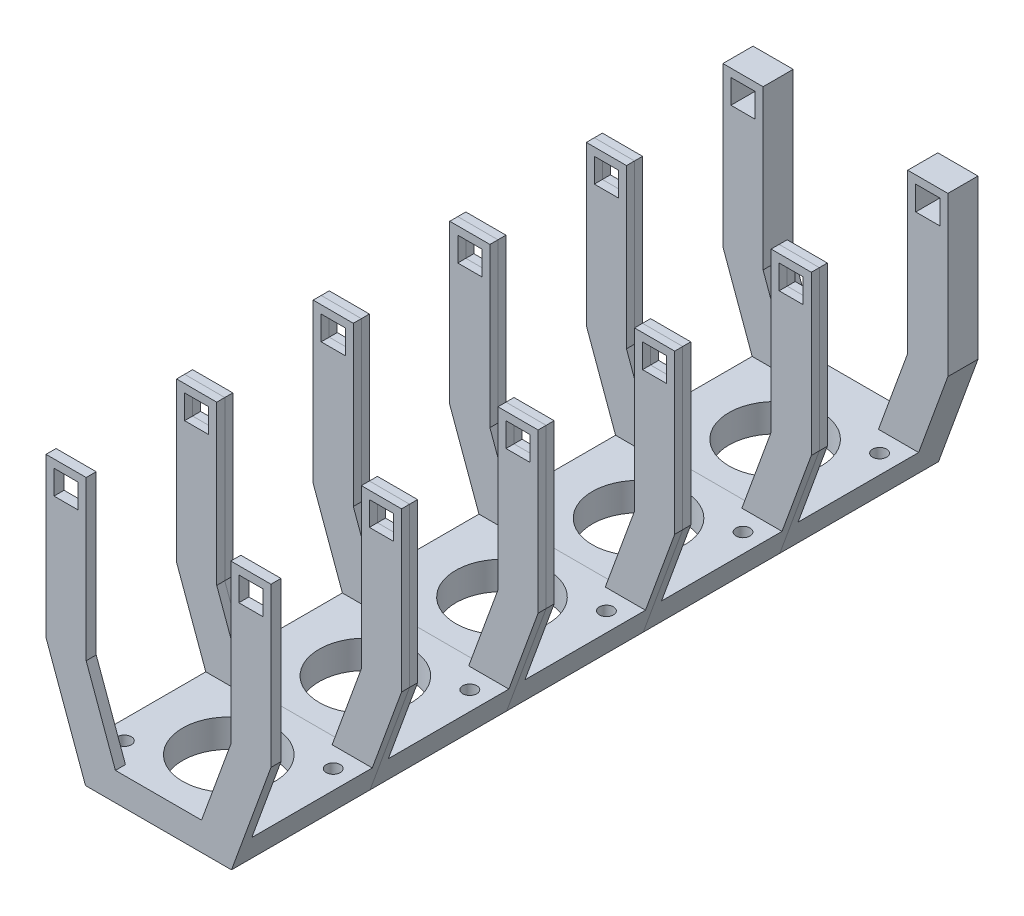
SolidWorks part; units mm, degrees
note: The reader was unsure of these and kept them because the rebuilt part matched: shared geometry of "Sketch3<4>".
ref_plane "Front Plane" through (0, 0, 0) normal (0, 0, 1) x (1, 0, 0)
ref_plane "Top Plane" through (0, 0, 0) normal (0, 1, 0) x (1, 0, 0)
ref_plane "Right Plane" through (0, 0, 0) normal (1, 0, 0) x (0, 0, -1)
sketch "Sketch3" plane through (0, 0, 0) normal (0, 0, 1) x (1, 0, 0)
  line L0 (0, 0) -> (46, 0) construction
  line L1 (-3, -3) -> (3, -3) construction
  line L2 (-3, -3) -> (-3, 3) construction
  line L3 (-3, 3) -> (3, 3) construction
  line L4 (3, -3) -> (3, 3) construction
  line L5 (-3, -3) -> (3, 3) construction
  line L6 (-3, 3) -> (3, -3) construction
  line L7 (43, -3) -> (49, -3) construction
  line L8 (43, -3) -> (43, 3) construction
  line L9 (43, 3) -> (49, 3) construction
  line L10 (49, -3) -> (49, 3) construction
  line L11 (43, -3) -> (49, 3) construction
  line L12 (43, 3) -> (49, -3) construction
  line L14 (5, -5) -> (5, 5)
  line L16 (-5, -5) -> (-5, 5)
  line L18 (51, -5) -> (51, 5)
  line L20 (41, -5) -> (41, 5)
  line L21 (-5, -5) -> (-5, -25) construction
  line L22 (-5, -25) -> (51, -25) construction
  line L23 (51, -25) -> (51, -5) construction
  line L24 (23, 0) -> (23, 5) construction
  line L25 (23, 5) -> (8, 5) construction
  line L26 (23, 5) -> (38, 5) construction
  line L27 (8, 5) -> (8, -25) construction
  line L28 (38, 5) -> (38, -25) construction
  line L29 (-5, -5) -> (4.8272, -32)
  line L30 (4.8272, -32) -> (41.1728, -32)
  line L31 (41.1728, -32) -> (51, -5)
  line L32 (5, -5) -> (12.2794, -25)
  line L33 (12.2794, -25) -> (33.7206, -25)
  line L34 (33.7206, -25) -> (41, -5)
  line L35 (2.2794, -25) -> (12.2794, -25)
  line L36 (-5, -5) -> (5, -5) construction
  line L37 (41, -5) -> (51, -5) construction
  line L38 (33.7206, -25) -> (43.7206, -25)
  line L39 (-5, 5) -> (5, 5) construction
  line L40 (41, 5) -> (51, 5) construction
  line L41 (-5, 5) -> (-5, 34.5)
  line L42 (-5, 34.5) -> (5, 34.5)
  line L43 (5, 34.5) -> (5, 5)
  line L44 (41, 5) -> (41, 34.5)
  line L45 (41, 34.5) -> (51, 34.5)
  line L46 (51, 34.5) -> (51, 5)
  line L48 (-3, 26.5) -> (3, 26.5)
  line L49 (-3, 26.5) -> (-3, 32.5)
  line L50 (-3, 32.5) -> (3, 32.5)
  line L51 (3, 26.5) -> (3, 32.5)
  line L52 (-3, 26.5) -> (3, 32.5) construction
  line L53 (-3, 32.5) -> (3, 26.5) construction
  line L54 (43, 26.5) -> (49, 26.5)
  line L55 (43, 26.5) -> (43, 32.5)
  line L56 (43, 32.5) -> (49, 32.5)
  line L57 (49, 26.5) -> (49, 32.5)
  line L58 (43, 26.5) -> (49, 32.5) construction
  line L59 (43, 32.5) -> (49, 26.5) construction
  point P0 (0, 0)
  point P6 (46, 0)
  point P27 (2.2794, -25)
  point P34 (43.7206, -25)
  point P35 (0, 29.5)
  point P46 (46, 29.5)
  point P51 (0, 29.8737)
  point P52 (46.4096, 29.8737)
  point P53 (2.2794, 29.8737)
  point P54 (0, 0)
  point P55 (0, 0)
  dimension "D1" = 40
  dimension "D2" = 6
  dimension "D4" = 30
  dimension "D5" = 30
  dimension "D6" = 7
  dimension "D7" = 20
  dimension "D8" = 20
  dimension "D9" = 20
  dimension "D10" = 20
  dimension "D11" = 29.5
  dimension "D12" = 29.5
  dimension "D13" = 2
  dimension "D14" = 2
  dimension "D3" = 2
extrude "Boss-Extrude1" add sketch "Sketch3" along normal blind 2
extrude "Boss-Extrude2" add sketch "Sketch3<4>" against normal blind 30 contours L38 L33 L35 L29 L30 L31
sketch "Sketch3<4>" plane through (0, 0, 0) normal (0, 0, 1) x (1, 0, 0) same geometry as "Sketch3"
sketch "Sketch4" plane through (0, 0, -30) normal (0, 0, -1) x (-1, 0, 0)
  line L0 (5, -5) -> (5, 34.5) construction
  line L2 (-5, -5) -> (-5, 34.5) construction
  line L3 (-5, -5) -> (-12.2794, -25) construction
  line L4 (5, -5) -> (-2.2794, -25) construction
  line L5 (-2.2794, -25) -> (-4.8272, -32) construction
  line L6 (-41.1728, -32) -> (-43.7206, -25) construction
  line L7 (-4.8272, -32) -> (-41.1728, -32) construction
  line L8 (-2.2794, -25) -> (-43.7206, -25) construction
  line L9 (-33.7206, -25) -> (-41, -5) construction
  line L10 (-41, -5) -> (-41, 34.5) construction
  line L11 (-43.7206, -25) -> (-51, -5) construction
  line L12 (-51, -5) -> (-51, 34.5) construction
  line L14 (5, -5) -> (5, 34.5)
  line L16 (-5, -5) -> (-5, 34.5)
  line L17 (-5, -5) -> (-12.2794, -25)
  line L18 (5, -5) -> (-2.2794, -25)
  line L19 (-2.2794, -25) -> (-4.8272, -32)
  line L20 (-41.1728, -32) -> (-43.7206, -25)
  line L21 (-4.8272, -32) -> (-41.1728, -32)
  line L22 (-12.2794, -25) -> (-33.7206, -25)
  line L23 (-33.7206, -25) -> (-41, -5)
  line L24 (-41, -5) -> (-41, 34.5)
  line L25 (-43.7206, -25) -> (-51, -5)
  line L26 (-51, -5) -> (-51, 34.5)
  line L44 (3, 32.5) -> (-3, 32.5) construction
  line L45 (3, 26.5) -> (3, 32.5) construction
  line L46 (3, 26.5) -> (-3, 26.5) construction
  line L47 (-3, 26.5) -> (-3, 32.5) construction
  line L48 (-49, 26.5) -> (-49, 32.5) construction
  line L49 (-43, 26.5) -> (-49, 26.5) construction
  line L50 (-43, 26.5) -> (-43, 32.5) construction
  line L51 (-43, 32.5) -> (-49, 32.5) construction
  line L52 (3, 32.5) -> (-3, 32.5)
  line L53 (3, 26.5) -> (3, 32.5)
  line L54 (3, 26.5) -> (-3, 26.5)
  line L55 (-3, 26.5) -> (-3, 32.5)
  line L56 (-49, 26.5) -> (-49, 32.5)
  line L57 (-43, 26.5) -> (-49, 26.5)
  line L58 (-43, 26.5) -> (-43, 32.5)
  line L59 (-43, 32.5) -> (-49, 32.5)
  line L60 (-51, 34.5) -> (-41, 34.5)
  line L61 (-5, 34.5) -> (5, 34.5)
extrude "Boss-Extrude6" add sketch "Sketch4" along normal blind 2
pattern_linear "LPattern7" count 5 spacing 34 along (0, 0, 1) of bodies 128
sketch "Sketch12" plane through (0, 0, -32) normal (0, 0, -1) x (-1, 0, 0)
  line L0 (-5, 34.5) -> (-5, -5) construction
  line L2 (5, -5) -> (5, 34.5) construction
  line L7 (-5, -5) -> (-12.2794, -25) construction
  line L8 (-4.8272, -32) -> (5, -5) construction
  line L9 (-12.2794, -25) -> (-33.7206, -25) construction
  line L10 (-41.1728, -32) -> (-4.8272, -32) construction
  line L11 (-41, -5) -> (-41, 34.5) construction
  line L12 (-33.7206, -25) -> (-41, -5) construction
  line L13 (-51, -5) -> (-41.1728, -32) construction
  line L18 (-51, 34.5) -> (-51, -5) construction
  line L20 (-5, 34.5) -> (-5, -5)
  line L22 (5, -5) -> (5, 34.5)
  line L27 (-5, -5) -> (-12.2794, -25)
  line L28 (-4.8272, -32) -> (5, -5)
  line L29 (-12.2794, -25) -> (-33.7206, -25)
  line L30 (-41.1728, -32) -> (-4.8272, -32)
  line L31 (-41, -5) -> (-41, 34.5)
  line L32 (-33.7206, -25) -> (-41, -5)
  line L33 (-51, -5) -> (-41.1728, -32)
  line L38 (-51, 34.5) -> (-51, -5)
  line L40 (-43, 32.5) -> (-49, 32.5) construction
  line L41 (-49, 32.5) -> (-49, 26.5) construction
  line L42 (-49, 26.5) -> (-43, 26.5) construction
  line L43 (-43, 26.5) -> (-43, 32.5) construction
  line L44 (-3, 26.5) -> (3, 26.5) construction
  line L45 (-3, 32.5) -> (-3, 26.5) construction
  line L46 (3, 32.5) -> (-3, 32.5) construction
  line L47 (3, 26.5) -> (3, 32.5) construction
  line L48 (-43, 32.5) -> (-49, 32.5)
  line L49 (-49, 32.5) -> (-49, 26.5)
  line L50 (-49, 26.5) -> (-43, 26.5)
  line L51 (-43, 26.5) -> (-43, 32.5)
  line L52 (-3, 26.5) -> (3, 26.5)
  line L53 (-3, 32.5) -> (-3, 26.5)
  line L54 (3, 32.5) -> (-3, 32.5)
  line L55 (3, 26.5) -> (3, 32.5)
  line L56 (-41, 34.5) -> (-51, 34.5) construction
  line L57 (-41, 34.5) -> (-51, 34.5)
  line L58 (5, 34.5) -> (-5, 34.5) construction
  line L59 (5, 34.5) -> (-5, 34.5)
extrude "Boss-Extrude7" add sketch "Sketch12" along normal blind 2
sketch "Sketch13" plane through (0, 0, 138) normal (0, 0, 1) x (1, 0, 0)
  line L1 (41, -5) -> (41, 34.5) construction
  line L4 (51, -5) -> (51, 34.5) construction
  line L7 (41.1728, -32) -> (51, -5) construction
  line L8 (33.7206, -25) -> (41, -5) construction
  line L9 (4.8272, -32) -> (41.1728, -32) construction
  line L10 (12.2794, -25) -> (33.7206, -25) construction
  line L11 (5, -5) -> (12.2794, -25) construction
  line L12 (-5, -5) -> (4.8272, -32) construction
  line L13 (5, -5) -> (5, 34.5) construction
  line L18 (-5, -5) -> (-5, 34.5) construction
  line L21 (41, -5) -> (41, 34.5)
  line L24 (51, -5) -> (51, 34.5)
  line L27 (41.1728, -32) -> (51, -5)
  line L28 (33.7206, -25) -> (41, -5)
  line L29 (4.8272, -32) -> (41.1728, -32)
  line L30 (12.2794, -25) -> (33.7206, -25)
  line L31 (5, -5) -> (12.2794, -25)
  line L32 (-5, -5) -> (4.8272, -32)
  line L33 (5, -5) -> (5, 34.5)
  line L38 (-5, -5) -> (-5, 34.5)
  line L40 (41, 34.5) -> (51, 34.5) construction
  line L41 (-5, 34.5) -> (5, 34.5) construction
  line L42 (41, 34.5) -> (51, 34.5)
  line L43 (-5, 34.5) -> (5, 34.5)
extrude "Boss-Extrude8" add sketch "Sketch13" along normal blind 0.5
sketch "Sketch15" plane through (0, -25, 0) normal (0, 1, 0) x (1, 0, 0)
  line L0 (23, -104) -> (23, -138.5) construction
  line L1 (12.2794, -104) -> (33.7206, -104) construction
  line L2 (33.7206, -138.5) -> (12.2794, -138.5) construction
  line L3 (2.2794, -121) -> (43.7206, -121) construction
  line L4 (2.2794, -106) -> (2.2794, -136) construction
  line L5 (43.7206, -106) -> (43.7206, -136) construction
  line L6 (7, -131) -> (23, -131) construction
  line L7 (7, -131) -> (7, -121) construction
  circle A0 centre (23, -121) radius 11.5
  circle A1 centre (23, -121) radius 16 construction
  circle A2 centre (7, -131) radius 1.75
  circle A3 centre (39, -111) radius 1.75
  dimension "D1" = 23
  dimension "D2" = 32
  dimension "D3" = 3.5
  dimension "D4" = 10
  dimension "D5" = 16
  dimension "D6" = 16
  dimension "D7" = 10
extrude "Cut-Extrude5" cut sketch "Sketch15" against normal up to surface (7 mm away)
pattern_linear "LPattern8" count 5 spacing 34 along (0, 0, -1) of "Cut-Extrude5"
sketch "Sketch17" plane through (0, 0, 138.5) normal (0, 0, 1) x (1, 0, 0)
  line L40 (-3, 26.5) -> (3, 26.5) construction
  line L41 (3, 26.5) -> (3, 32.5) construction
  line L42 (-3, 26.5) -> (-3, 32.5) construction
  line L43 (-3, 32.5) -> (3, 32.5) construction
  line L44 (49, 26.5) -> (49, 32.5) construction
  line L45 (43, 26.5) -> (49, 26.5) construction
  line L46 (43, 26.5) -> (43, 32.5) construction
  line L47 (43, 32.5) -> (49, 32.5) construction
  line L48 (-3, 26.5) -> (3, 26.5)
  line L49 (3, 26.5) -> (3, 32.5)
  line L50 (-3, 26.5) -> (-3, 32.5)
  line L51 (-3, 32.5) -> (3, 32.5)
  line L52 (49, 26.5) -> (49, 32.5)
  line L53 (43, 26.5) -> (49, 26.5)
  line L54 (43, 26.5) -> (43, 32.5)
  line L55 (43, 32.5) -> (49, 32.5)
extrude "Cut-Extrude6" cut sketch "Sketch17" against normal blind 5.5
sketch "Sketch18" plane through (0, 0, -34) normal (0, 0, -1) x (-1, 0, 0)
  line L0 (5, -5) -> (5, 34.5) construction
  line L2 (-5, 34.5) -> (-5, -5) construction
  line L7 (-4.8272, -32) -> (5, -5) construction
  line L8 (-5, -5) -> (-12.2794, -25) construction
  line L9 (-41.1728, -32) -> (-4.8272, -32) construction
  line L10 (-12.2794, -25) -> (-33.7206, -25) construction
  line L11 (-33.7206, -25) -> (-41, -5) construction
  line L12 (-51, -5) -> (-41.1728, -32) construction
  line L13 (-51, 34.5) -> (-51, -5) construction
  line L18 (-41, -5) -> (-41, 34.5) construction
  line L20 (5, -5) -> (5, 34.5)
  line L22 (-5, 34.5) -> (-5, -5)
  line L27 (-4.8272, -32) -> (5, -5)
  line L28 (-5, -5) -> (-12.2794, -25)
  line L29 (-41.1728, -32) -> (-4.8272, -32)
  line L30 (-12.2794, -25) -> (-33.7206, -25)
  line L31 (-33.7206, -25) -> (-41, -5)
  line L32 (-51, -5) -> (-41.1728, -32)
  line L33 (-51, 34.5) -> (-51, -5)
  line L38 (-41, -5) -> (-41, 34.5)
  line L40 (5, 34.5) -> (-5, 34.5) construction
  line L41 (-41, 34.5) -> (-51, 34.5) construction
  line L50 (5, 34.5) -> (-5, 34.5)
  line L51 (-41, 34.5) -> (-51, 34.5)
  line L64 (3, 26.5) -> (3, 32.5) construction
  line L65 (3, 32.5) -> (-3, 32.5) construction
  line L66 (-3, 32.5) -> (-3, 26.5) construction
  line L67 (-3, 26.5) -> (3, 26.5) construction
  line L68 (-49, 26.5) -> (-43, 26.5) construction
  line L69 (-43, 26.5) -> (-43, 32.5) construction
  line L70 (-43, 32.5) -> (-49, 32.5) construction
  line L71 (-49, 32.5) -> (-49, 26.5) construction
  line L72 (-3, 32.5) -> (-3, 26.5)
  line L73 (3, 32.5) -> (-3, 32.5)
  line L74 (3, 26.5) -> (3, 32.5)
  line L75 (-3, 26.5) -> (3, 26.5)
  line L76 (-49, 32.5) -> (-49, 26.5)
  line L77 (-43, 32.5) -> (-49, 32.5)
  line L78 (-43, 26.5) -> (-43, 32.5)
  line L79 (-49, 26.5) -> (-43, 26.5)
extrude "Boss-Extrude9" add sketch "Sketch18" along normal blind 3.5
